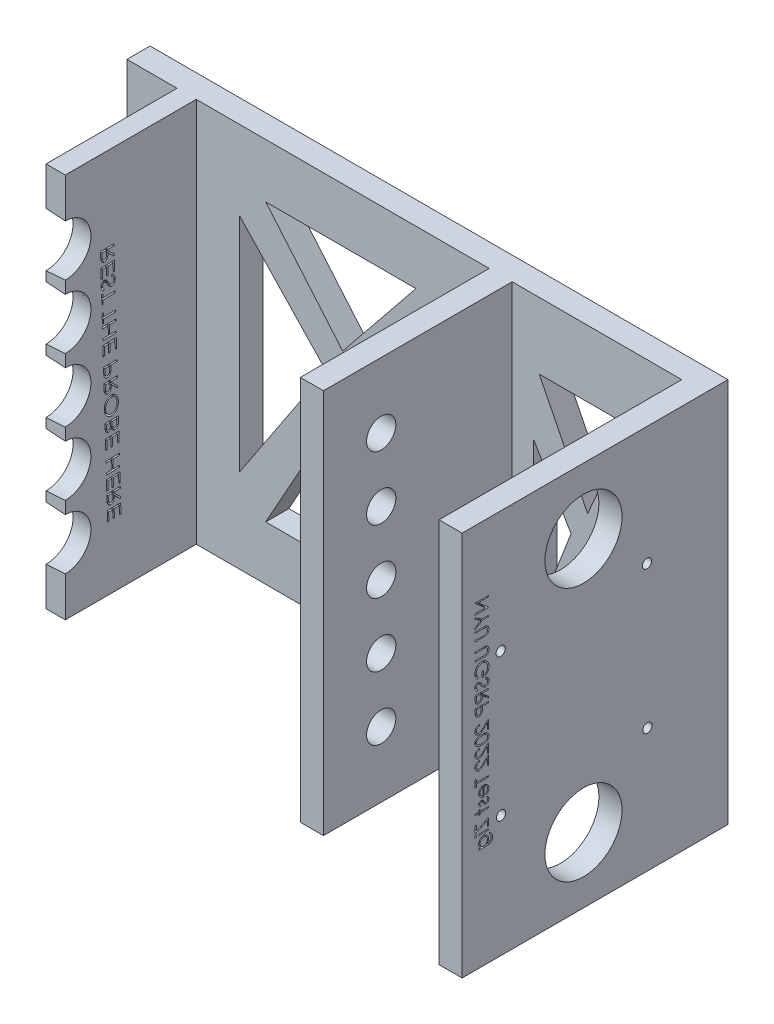
SolidWorks part; units mm, degrees
ref_plane "Front Plane" through (0, 0, 0) normal (0, 0, 1) x (1, 0, 0)
ref_plane "Top Plane" through (0, 0, 0) normal (0, 1, 0) x (1, 0, 0)
ref_plane "Right Plane" through (0, 0, 0) normal (1, 0, 0) x (0, 0, -1)
sketch "Sketch1" plane through (0, 0, 0) normal (0, 0, 1) x (1, 0, 0)
  line L1 (75, -50) -> (-75, -50)
  line L2 (75, -50) -> (75, 50)
  line L3 (75, 50) -> (-75, 50)
  line L4 (-75, -50) -> (-75, 50)
  line L5 (75, -50) -> (-75, 50) construction
  line L6 (75, 50) -> (-75, -50) construction
  line L7 (69, -50) -> (75, -50)
  line L8 (69, -50) -> (69, 50)
  line L9 (69, 50) -> (75, 50)
  line L10 (75, -50) -> (75, 50)
  line L11 (25, -50) -> (19, -50)
  line L12 (25, -50) -> (25, 50)
  line L13 (25, 50) -> (19, 50)
  line L14 (19, -50) -> (19, 50)
  line L15 (-57, -50) -> (-62, -50)
  line L16 (-57, -50) -> (-57, 50)
  line L17 (-57, 50) -> (-62, 50)
  line L18 (-62, -50) -> (-62, 50)
  line L51 (69, -46) -> (69, 36.1961)
  point P0 (0, 0)
  point P7 (0, 50)
  dimension "D1" = 100
  dimension "D2" = 150
  dimension "D3" = 6
  dimension "D4" = 0
  dimension "D5" = 13
  dimension "D6" = 5
  dimension "D7" = 76
  dimension "D8" = 6
extrude "Boss-Extrude3" add sketch "Sketch1" against normal blind 6 contours L3 L4 L1 L2
extrude "Boss-Extrude4" add sketch "Sketch1<5>" along normal blind 49 contours L14 L1 L12 L3 region at (22, 0, 0)
sketch "Sketch1<5>" plane through (0, 0, 0) normal (0, 0, 1) x (1, 0, 0) same geometry as "Sketch1"
extrude "Boss-Extrude5" add sketch "Sketch1<6>" along normal blind 63 contours L1 L10 L3 L8 region at (72, 0, 0)
sketch "Sketch1<6>" plane through (0, 0, 0) normal (0, 0, 1) x (1, 0, 0) same geometry as "Sketch1"
extrude "Boss-Extrude6" add sketch "Sketch1<7>" along normal blind 34 contours L18 L17 L16 L15
sketch "Sketch1<7>" plane through (0, 0, 0) normal (0, 0, 1) x (1, 0, 0) same geometry as "Sketch1"
sketch "Sketch3" plane through (-62, 0, 0) normal (-1, 0, 0) x (0, 0, 1)
  line L2 (34, -50) -> (34, 50) construction
  circle A0 centre (34, 0) radius 7
  circle A1 centre (34, 33) radius 7
  circle A2 centre (34, -33) radius 7
  circle A3 centre (34, 16.5) radius 7
  circle A4 centre (34, -16.5) radius 7
  dimension "D1" = 33
  dimension "D2" = 33
  dimension "D3" = 16.5
  dimension "D4" = 16.5
extrude "Cut-Extrude5" cut sketch "Sketch3" against normal blind 78 draft 4
sketch "Sketch4" plane through (69, 0, 0) normal (-1, 0, 0) x (0, 0, 1)
  line L0 (63, -50) -> (63, 50) construction
  line L1 (56.1117, 33) -> (56.1117, -33) construction
  line L6 (63, 0) -> (0, 0) construction
  circle A2 centre (31.5, 33) radius 10
  circle A3 centre (31.5, -33) radius 10
  text T0 "NYU UGSRP 2022 Test Zig"
  point P6 (52.9967, 18.5)
  point P7 (52.9144, -18.5)
  point P8 (14.9206, -17.8144)
  point P9 (15.0029, 19.1856)
  point P10 (31.5, 0)
  dimension "D1" = 33
  dimension "D2" = 18.5
  dimension "D3" = 18.5
  dimension "D4" = 38
  dimension "D6" = 38
  dimension "D7" = 37
extrude "Cut-Extrude6" cut sketch "Sketch4" against normal blind 80
hole_wizard "M2 Clearance Hole3" positions "3DSketch1" profile "Sketch14" hole size "M2" standard "ANSI Metric" end condition through all
sketch3d "3DSketch1"
  point P0 (69, 18.5, 52.9967)
  point P3 (69, -18.5, 52.9144)
  point P6 (69, 19.1856, 15.0029)
sketch "Sketch14" plane through (69, 18.5, 52.9967) normal (0, 1, 0) x (0, 0, 1)
  line L0 (0, 0) -> (0, 6)
  line L1 (0, 6) -> (1.2, 6)
  line L2 (1.2, 6) -> (1.2, 0.025)
  line L3 (1.2, 0.025) -> (1.225, 0)
  line L5 (1.225, 0) -> (0, 0)
  line L6 (-1.2, 0.025) -> (-1.225, 0) construction
  line L11 (0, -6.35) -> (0, 107.95) construction
  dimension "Thru Hole Dia." = 2.4
  dimension "Thru Hole Depth" = 6
  dimension "Near C'Sink Dia." = 2.45
  dimension "Near C'Sink Angle" = 90
hole_wizard "M2 Clearance Hole4" positions "3DSketch3" profile "Sketch16" hole size "M2" standard "ANSI Metric" end condition through all
sketch3d "3DSketch3"
  point P0 (69, -17.8144, 14.9206)
sketch "Sketch16" plane through (69, -17.8144, 14.9206) normal (0, 1, 0) x (0, 0, 1)
  line L0 (0, 0) -> (0, 6)
  line L1 (0, 6) -> (1.2, 6)
  line L2 (1.2, 6) -> (1.2, 0.025)
  line L3 (1.2, 0.025) -> (1.225, 0)
  line L5 (1.225, 0) -> (0, 0)
  line L6 (-1.2, 0.025) -> (-1.225, 0) construction
  line L11 (0, -6.35) -> (0, 107.95) construction
  dimension "Thru Hole Dia." = 2.4
  dimension "Thru Hole Depth" = 6
  dimension "Near C'Sink Dia." = 2.45
  dimension "Near C'Sink Angle" = 90
sketch "Sketch18" plane through (-62, 0, 0) normal (-1, 0, 0) x (0, 0, 1)
  line L0 (21.3976, 28.8042) -> (19.5206, -34.4898) construction
  text T0 "REST THE PROBE HERE" font "Century Gothic" height 3.5
extrude "Cut-Extrude8" cut sketch "Sketch18" against normal up to next (5 mm away)
sketch "Sketch20" plane through (19, 0, 0) normal (-1, 0, 0) x (0, 0, 1)
  circle A0 centre (34, 33) radius 3.8
  circle A1 centre (34, 16.5) radius 3.8
  circle A2 centre (34, 0) radius 3.8
  circle A3 centre (34, -33) radius 3.8
  circle A4 centre (34, -16.5) radius 3.8
  point P5 (34, 19.0608)
  point P8 (34, 0)
  point P13 (34, -19.6967)
  point P14 (34, -38.1419)
  dimension "D1" = 7.6
  dimension "D2" = 16.5
  dimension "D3" = 33
  dimension "D4" = 16.5
  dimension "D5" = 16.5
extrude "Cut-Extrude9" cut sketch "Sketch20" against normal blind 10
sketch "Sketch25" plane through (0, 0, 0) normal (0, 0, 1) x (1, 0, 0)
  line L0 (-45.744, -28.1025) -> (-45.744, 29.4197)
  line L9 (-45.744, 29.4197) -> (-23.3006, 5.7846)
  line L10 (-23.3006, 5.7846) -> (-45.744, -28.1025)
  line L11 (-38.9788, 35.9731) -> (0, 35.9731)
  line L12 (0, 35.9731) -> (-19, 12.4207)
  line L13 (-19, 12.4207) -> (-38.9788, 35.9731)
  line L14 (-38.9788, -35.9731) -> (-19, 0)
  line L15 (-19, 0) -> (0, -35.9731)
  line L16 (0, -35.9731) -> (-38.9788, -35.9731)
  line L17 (7.744, 29.4197) -> (-14.4665, 6.098)
  line L18 (-14.4665, 6.098) -> (7.744, -28.1025)
  line L19 (7.744, -28.1025) -> (7.744, 29.4197)
  point P6 (-19, 0)
  point P11 (0, 35.9731)
  point P12 (7.744, 29.4197)
  point P13 (-45.744, 29.4197)
  point P14 (0, -35.9731)
  point P15 (-38.9788, -35.9731)
  point P16 (-38.9788, 35.9731)
  point P17 (-45.744, -28.1025)
  point P18 (7.744, -28.1025)
  point P19 (-14.4665, 6.098)
  point P20 (0, 0)
  point P21 (-23.3006, 5.7846)
  point P22 (0, 0)
  point P23 (0, 0)
  point P24 (-19, 12.4207)
  point P25 (0, 0)
  point P26 (0, 0)
  point P34 (0, 0)
extrude "Cut-Extrude14" cut sketch "Sketch25" against normal blind 74
sketch "Sketch27" plane through (0, 0, 0) normal (0, 0, 1) x (1, 0, 0)
  line L0 (30.5783, -23.9717) -> (30.5783, 17.2974)
  line L1 (30.5783, 17.2974) -> (40.2795, 1.0225)
  line L2 (40.2795, 1.0225) -> (30.5783, -23.9717)
  line L3 (32.0076, 32.7552) -> (55.4444, 32.7552)
  line L4 (55.4444, 32.7552) -> (44.5801, 7.6585)
  line L5 (44.5801, 7.6585) -> (32.0076, 32.7552)
  line L6 (32.4167, -39.9915) -> (44.5801, -4.7621)
  line L7 (44.5801, -4.7621) -> (63.1873, -39.9915)
  line L8 (63.1873, -39.9915) -> (32.4167, -39.9915)
  line L9 (63.9186, 32.7552) -> (49.1136, 1.3359)
  line L10 (49.1136, 1.3359) -> (63.9186, -23.9717)
  line L11 (63.9186, -23.9717) -> (63.9186, 32.7552)
  point P12 (30.4437, 21.9271)
  point P13 (28.6743, -9.6286)
  point P14 (58.0344, -9.6286)
  point P15 (59.8377, 24.8953)
  point P16 (28.6743, -29.3094)
  point P17 (28.6743, 42.6205)
  point P18 (51.702, 43.4372)
  point P19 (60.1762, 43.4372)
  point P20 (26.8359, -13.2897)
extrude "Cut-Extrude15" cut sketch "Sketch27" against normal blind 74
